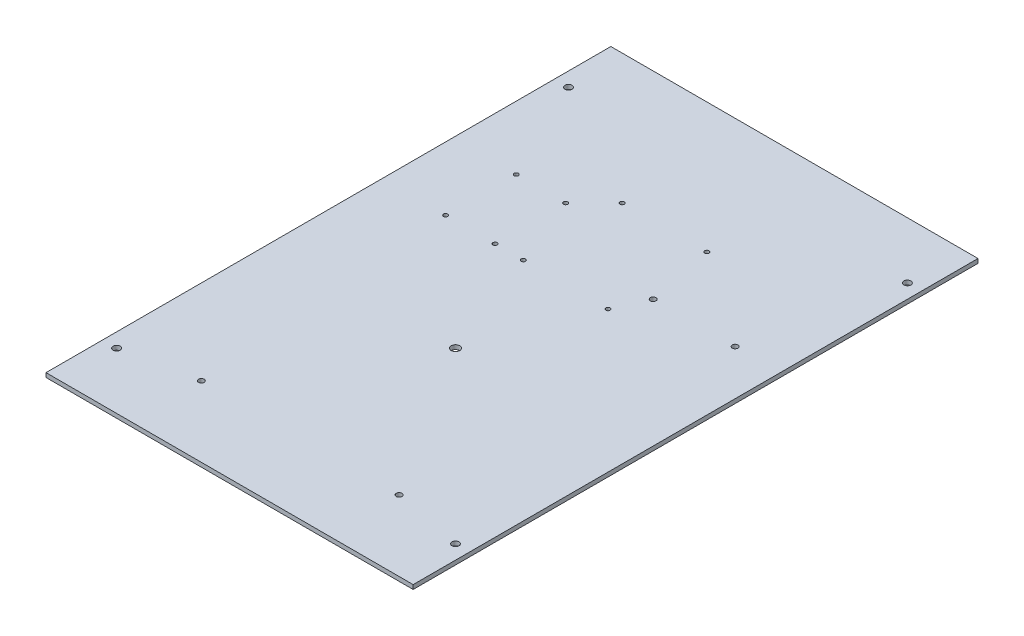
SolidWorks part; units mm, degrees
ref_plane "Front Plane" through (0, 0, 0) normal (0, 0, 1) x (1, 0, 0)
ref_plane "Top Plane" through (0, 0, 0) normal (0, 1, 0) x (1, 0, 0)
ref_plane "Right Plane" through (0, 0, 0) normal (1, 0, 0) x (0, 0, -1)
sketch "Sketch1" plane through (0, 0, 0) normal (0, 1, 0) x (1, 0, 0)
  line L1 (0, 0) -> (260, 0)
  line L2 (0, 0) -> (0, 400)
  line L3 (0, 400) -> (260, 400)
  line L4 (260, 0) -> (260, 400)
  circle A0 centre (130, 160) radius 3
  circle A2 centre (100, 238) radius 1.5
  circle A3 centre (160, 238) radius 1.5
  circle A4 centre (160, 308) radius 1.5
  circle A5 centre (100, 308) radius 1.5
  circle A6 centre (80, 238) radius 1.5
  circle A7 centre (45, 238) radius 1.5
  circle A8 centre (45, 288) radius 1.5
  circle A9 centre (80, 288) radius 1.5
  circle A10 centre (170, 260) radius 2
  circle A11 centre (228, 260) radius 2
  circle A12 centre (10, 360) radius 2.5
  circle A13 centre (250, 360) radius 2.5
  circle A14 centre (250, 40) radius 2.5
  circle A15 centre (10, 40) radius 2.5
  circle A16 centre (200, 50) radius 2
  circle A17 centre (60, 50) radius 2
  dimension "D5" = 6
  dimension "D15" = 5
  dimension "D18" = 5
  dimension "D19" = 5
  dimension "D20" = 5
  dimension "D27" = 4
  dimension "D35" = 3
  dimension "D36" = 4
  dimension "D2" = 400
  dimension "D3" = 260
  dimension "D4" = 240
  dimension "D6" = 58
  dimension "D7" = 78
  dimension "D8" = 60
  dimension "D9" = 70
  dimension "D10" = 22
  dimension "D12" = 35
  dimension "D13" = 50
  dimension "D14" = 30
  dimension "D16" = 10
  dimension "D17" = 40
  dimension "D21" = 10
  dimension "D22" = 40
  dimension "D23" = 40
  dimension "D24" = 10
  dimension "D25" = 40
  dimension "D26" = 10
  dimension "D28" = 60
  dimension "D29" = 50
  dimension "D31" = 60
  dimension "D32" = 50
  dimension "D33" = 130
  dimension "D11" = 50
  dimension "D34" = 32
extrude "Boss-Extrude1" add sketch "Sketch1" along normal blind 3 contours L1 L4 L3 L2 A11 A10 A9 A8 A7 A6 A5 A4 A3 A2 A0 region at (130.0017, 0, -199.9956)
equation "\"D33@Sketch1\"=\"D3@Sketch1\"/2"
equation "\"D18@Sketch1\"=\"D15@Sketch1\""
equation "\"D19@Sketch1\"=\"D15@Sketch1\""
equation "\"D20@Sketch1\"=\"D15@Sketch1\""
